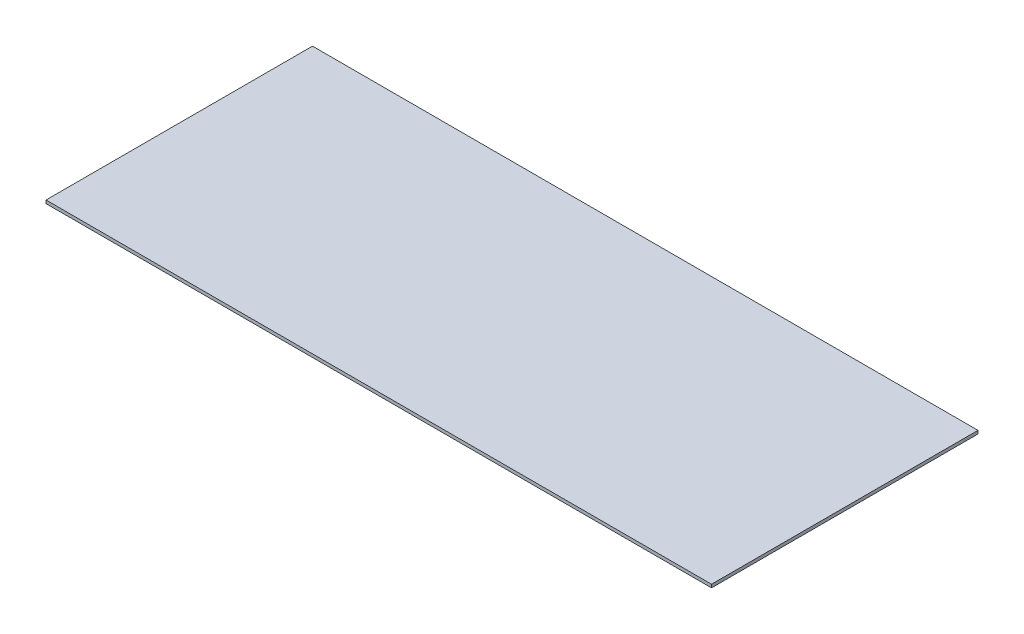
SolidWorks part; units mm, degrees
ref_plane "Front Plane" through (0, 0, 0) normal (0, 0, 1) x (1, 0, 0)
ref_plane "Top of Plywood" through (0, 0, 0) normal (0, 1, 0) x (1, 0, 0)
ref_plane "Right Plane" through (0, 0, 0) normal (1, 0, 0) x (0, 0, -1)
sketch "Interior Dim" plane through (0, 0, 0) normal (0, 1, 0) x (1, 0, 0)
  line L1 (0, 0) -> (5867.4, 0)
  line L2 (0, 0) -> (0, 2349.5)
  line L3 (0, 2349.5) -> (5867.4, 2349.5)
  line L4 (5867.4, 0) -> (5867.4, 2349.5)
  dimension "D1" = 5867.4
  dimension "D2" = 2349.5
sketch "Stud Centerlines" plane through (0, 0, 0) normal (0, 1, 0) x (1, 0, 0)
  line L0 (19.05, 19.05) -> (19.05, 2330.45) construction
  line L1 (19.05, 2330.45) -> (5867.4, 2330.45) construction
  line L2 (5867.4, 0) -> (5867.4, 2349.5) construction
  line L3 (5867.4, 19.05) -> (19.05, 19.05) construction
  line L4 (0, 0) -> (0, 2349.5) construction
  line L5 (0, 2349.5) -> (5867.4, 2349.5) construction
  line L6 (0, 0) -> (5867.4, 0) construction
  line L8 (4121.15, 2330.45) -> (4121.15, 19.05) construction
  line L9 (1771.65, 2330.45) -> (1771.65, 19.05) construction
  line L10 (19.05, 2051.05) -> (4121.15, 2051.05) construction
  dimension "D1" = 19.05
  dimension "D2" = 19.05
  dimension "D3" = 19.05
  dimension "D5" = 279.4
  dimension "D6" = 1752.6
  dimension "D7" = 2349.5
sketch "Gypsum Board" plane through (0, 0, 0) normal (0, 1, 0) x (1, 0, 0)
  line L0 (38.1, 38.1) -> (38.1, 2311.4)
  line L1 (38.1, 2311.4) -> (5867.4, 2311.4)
  line L2 (5867.4, 0) -> (5867.4, 2349.5) construction
  line L3 (50.8, 2298.7) -> (50.8, 50.8)
  line L4 (38.1, 38.1) -> (5867.4, 38.1)
  line L5 (50.8, 50.8) -> (5867.4, 50.8)
  line L6 (19.05, 19.05) -> (19.05, 2330.45) construction
  line L7 (19.05, 2330.45) -> (5867.4, 2330.45) construction
  line L8 (5867.4, 19.05) -> (19.05, 19.05) construction
  line L9 (4165.6, 50.8) -> (4165.6, 2095.5)
  line L10 (50.8, 2298.7) -> (5867.4, 2298.7)
  line L11 (4165.6, 2095.5) -> (4178.3, 2095.5)
  line L12 (4178.3, 2095.5) -> (4178.3, 50.8)
  line L13 (4121.15, 2330.45) -> (4121.15, 19.05) construction
  line L14 (19.05, 2051.05) -> (4121.15, 2051.05) construction
  line L15 (5867.4, 2311.4) -> (5867.4, 2298.7)
  line L16 (5867.4, 50.8) -> (5867.4, 38.1)
  line L17 (4165.6, 50.8) -> (4178.3, 50.8)
  dimension "D1" = 19.05
  dimension "D2" = 19.05
  dimension "D3" = 12.7
  dimension "D4" = 12.7
  dimension "D5" = 12.7
  dimension "D6" = 19.05
  dimension "D7" = 44.45
  dimension "D8" = 12.7
  dimension "D9" = 44.45
sketch "PVC" plane through (0, 0, 0) normal (0, 1, 0) x (1, 0, 0)
  line L0 (50.8, 50.8) -> (50.8, 2006.6)
  line L1 (4076.7, 50.8) -> (1841.5, 50.8)
  line L2 (50.8, 50.8) -> (1701.8, 50.8)
  line L3 (1701.8, 50.8) -> (1701.8, 2006.6)
  line L4 (1701.8, 2006.6) -> (50.8, 2006.6)
  line L5 (50.8, 2298.7) -> (50.8, 50.8) construction
  line L6 (19.05, 2051.05) -> (4121.15, 2051.05) construction
  line L7 (1771.65, 2330.45) -> (1771.65, 19.05) construction
  line L8 (50.8, 50.8) -> (5867.4, 50.8) construction
  line L9 (63.5, 1993.9) -> (1689.1, 1993.9)
  line L10 (1689.1, 1993.9) -> (1689.1, 63.5)
  line L11 (1689.1, 63.5) -> (63.5, 63.5)
  line L12 (63.5, 63.5) -> (63.5, 1993.9)
  line L13 (1841.5, 2006.6) -> (4076.7, 2006.6)
  line L14 (4076.7, 2006.6) -> (4076.7, 50.8)
  line L15 (1841.5, 50.8) -> (1841.5, 2006.6)
  line L16 (4121.15, 2330.45) -> (4121.15, 19.05) construction
  line L17 (1854.2, 1993.9) -> (1854.2, 63.5)
  line L18 (1854.2, 63.5) -> (4064, 63.5)
  line L19 (4064, 63.5) -> (4064, 1993.9)
  line L20 (4064, 1993.9) -> (1854.2, 1993.9)
  dimension "D1" = 0
  dimension "D2" = 44.45
  dimension "D3" = 69.85
  dimension "D4" = 0
  dimension "D5" = 12.7
  dimension "D6" = 12.7
  dimension "D7" = 12.7
  dimension "D8" = 12.7
  dimension "D9" = 69.85
  dimension "D10" = 44.45
  dimension "D11" = 12.7
  dimension "D12" = 12.7
  dimension "D13" = 12.7
  dimension "D14" = 12.7
sketch "Open Indoor Space" plane through (0, 0, 0) normal (0, 1, 0) x (1, 0, 0)
  line L0 (4178.3, 2095.5) -> (4165.6, 2095.5)
  line L1 (63.5, 63.5) -> (1689.1, 63.5)
  line L2 (63.5, 63.5) -> (63.5, 1993.9)
  line L3 (63.5, 1993.9) -> (1689.1, 1993.9)
  line L4 (1689.1, 63.5) -> (1689.1, 1993.9)
  line L5 (1854.2, 63.5) -> (4064, 63.5)
  line L6 (1854.2, 63.5) -> (1854.2, 1993.9)
  line L7 (1854.2, 1993.9) -> (4064, 1993.9)
  line L8 (4064, 63.5) -> (4064, 1993.9)
  line L9 (4165.6, 2095.5) -> (50.8, 2095.5)
  line L10 (50.8, 2298.7) -> (50.8, 50.8) construction
  line L11 (50.8, 2095.5) -> (50.8, 2298.7)
  line L12 (50.8, 2298.7) -> (5867.4, 2298.7)
  line L13 (5867.4, 2298.7) -> (5867.4, 50.8)
  line L14 (5867.4, 50.8) -> (4178.3, 50.8)
  line L15 (4178.3, 50.8) -> (4178.3, 2095.5)
ref_plane "Interior Roof" through (0, 2381.25, 0) normal (0, 1, 0) x (1, 0, 0)
sketch "Sketch4" plane through (0, 0, 0) normal (0, 1, 0) x (1, 0, 0)
  line L1 (0, 0) -> (5867.4, 0)
  line L2 (0, 0) -> (0, 2349.5)
  line L3 (0, 2349.5) -> (5867.4, 2349.5)
  line L4 (5867.4, 0) -> (5867.4, 2349.5)
extrude "Boss-Extrude2" add sketch "Sketch4" against normal blind 27.94
sketch "Sketch5" plane through (0, 0, 0) normal (0, 1, 0) x (1, 0, 0)
  line L0 (177.8, 63.5) -> (177.8, 0)
  line L1 (1689.1, 63.5) -> (63.5, 63.5) construction
  line L2 (0, 0) -> (5867.4, 0) construction
  line L3 (1168.4, 63.5) -> (1168.4, 0)
  line L4 (3022.6, 63.5) -> (3022.6, 0)
  line L5 (19.05, 19.05) -> (19.05, 2330.45) construction
  line L6 (1930.4, 63.5) -> (1930.4, 0)
  line L7 (1771.65, 2330.45) -> (1771.65, 19.05) construction
  dimension "D1" = 990.6
  dimension "D2" = 158.75
  dimension "D3" = 158.75
  dimension "D4" = 1092.2
ref_plane "Top of Interior Roof" through (0, 2266.95, 0) normal (0, 1, 0) x (1, 0, 0)
ref_plane "Top of Insulated Subfloor" through (0, 40.64, 0) normal (0, 1, 0) x (1, 0, 0)
ref_plane "Top of Vinyl Flooring" through (0, 43.815, 0) normal (0, 1, 0) x (1, 0, 0)
sketch "Bathroom Floorspace" plane through (0, 0, 0) normal (0, 1, 0) x (1, 0, 0)
  line L1 (63.5, 1993.9) -> (1689.1, 1993.9)
  line L2 (63.5, 1993.9) -> (63.5, 63.5)
  line L3 (63.5, 63.5) -> (1689.1, 63.5)
  line L4 (1689.1, 1993.9) -> (1689.1, 63.5)
  line L5 (1854.2, 1993.9) -> (4064, 1993.9)
  line L6 (1854.2, 1993.9) -> (1854.2, 63.5)
  line L7 (1854.2, 63.5) -> (4064, 63.5)
  line L8 (4064, 1993.9) -> (4064, 63.5)
